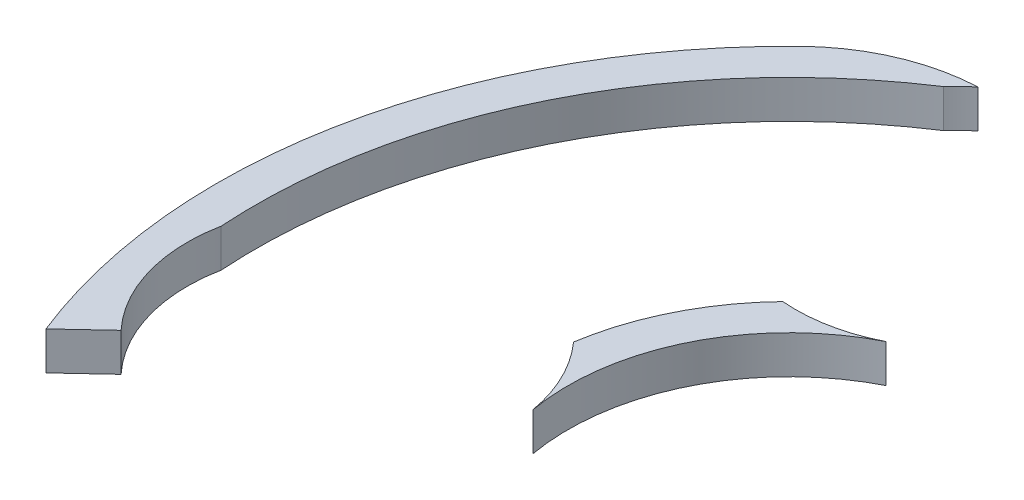
SolidWorks part; units mm, degrees
ref_plane "Plan de face" through (0, 0, 0) normal (0, 0, 1) x (1, 0, 0)
ref_plane "Plan de dessus" through (0, 0, 0) normal (0, 1, 0) x (1, 0, 0)
ref_plane "Plan de droite" through (0, 0, 0) normal (1, 0, 0) x (0, 0, -1)
sketch "Esquisse1" plane through (0, 0, 0) normal (0, 1, 0) x (1, 0, 0)
  line L0 (-85.9864, -39.221) -> (-80.901, -34.4645)
  line L3 (-9.4508, 5.6286) -> (-14.9085, -3.5351) construction
  line L5 (3.3105, -15.9387) -> (9.4508, -5.6286) construction
  line L12 (0, 0) -> (-80, 0) construction
  line L13 (-64.4502, -24.994) -> (-51.2217, 24.3754) construction
  line L14 (-65, 0) -> (-64.4502, -24.994) construction
  arc A0 (-44.8834, -16.4709) -> (3.3105, -15.9387) centre (-21.2415, 25) ccw construction
  arc A1 (-20.1052, -3.4627) -> (-14.9085, -3.5351) centre (-17.486, -2) ccw construction
  arc A2 (-20.1052, -3.4627) -> (-29.494, 14.405) centre (325.5264, 189.5538) cw construction
  arc A3 (-13.5326, 17.4331) -> (-23.8264, -39.4451) centre (-16.3245, -11.4322) ccw
  arc A4 (-40.7805, 12.1878) -> (-49.9076, -6.124) centre (-16.3245, -11.4322) ccw
  arc A5 (-13.0513, 22.4098) -> (-25.1198, -44.2749) centre (-16.3245, -11.4322) ccw construction
  arc A6 (-54.6669, 47.1327) -> (-86.1705, -16.0732) centre (-16.3245, -11.4322) ccw
  arc A36 (-51.2217, 24.3754) -> (-64.4502, -24.994) centre (-16.3245, -11.4322) ccw construction
  arc A37 (-68.6703, 42.2792) -> (-85.9864, -39.221) centre (-16.3245, -11.4322) ccw
  arc A41 (9.4508, -5.6286) -> (-9.4508, 5.6286) centre (0, 0) ccw construction
  arc A42 (-16.402, 38.5677) -> (-47.4539, -50.5598) centre (-16.3245, -11.4322) ccw construction
  arc A43 (-52.3505, 49.3499) -> (-29.494, 14.405) centre (-39.0306, 33.1147) ccw
  arc A44 (-52.3505, 49.3499) -> (-68.6703, 42.2792) centre (-51.2217, 24.3754) ccw
  arc A45 (-44.8834, -16.4709) -> (-80.901, -34.4645) centre (-65.564, -20.1196) ccw
  point P78 (-56.6847, 2.6915)
  point P85 (-65, 0)
  dimension "D4" = 25
  dimension "D5" = 12
  dimension "D6" = 21
  dimension "D7" = 5
  dimension "D8" = 25
  dimension "D9" = 5
  dimension "D10" = 3
  dimension "D11" = 17.6
  dimension "D18" = 80
  dimension "D20" = 75
  dimension "D26" = 11
  dimension "D13" = 50
  dimension "D14" = 21
  dimension "D12" = 2
  dimension "D22" = 25
  dimension "D23" = 75
  dimension "D24" = 28
  dimension "D25" = 15
  dimension "D30" = 15
  dimension "D32" = 5
extrude "Boss.-Extru.1" add sketch "Esquisse1" along normal blind 5 contours A45 A3 A43 A44 A37 L0 | A45 A3 A43 A4 region at (-88.7404, 0, -3.9537) region at (-43.5346, 0, -2.13)
